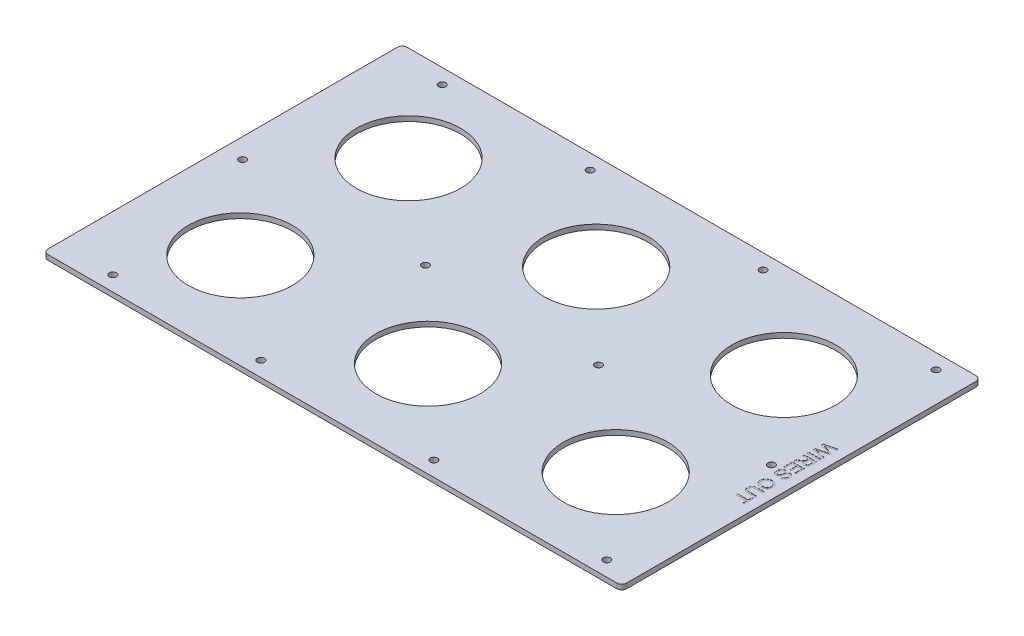
SolidWorks part; units mm, degrees
material "ABS"
ref_plane "Front" through (0, 0, 0) normal (0, 0, 1) x (1, 0, 0)
ref_plane "Top" through (0, 0, 0) normal (0, 1, 0) x (1, 0, 0)
ref_plane "Right" through (0, 0, 0) normal (1, 0, 0) x (0, 0, -1)
sketch "Sketch1" plane through (0, 0, 0) normal (0, 1, 0) x (1, 0, 0)
  line L1 (-180.975, 114.3) -> (180.975, 114.3)
  line L2 (-184.15, 111.125) -> (-184.15, -111.125)
  line L3 (-180.975, -114.3) -> (180.975, -114.3)
  line L4 (184.15, 111.125) -> (184.15, -111.125)
  line L5 (-184.15, 114.3) -> (184.15, -114.3) construction
  line L6 (-184.15, -114.3) -> (184.15, 114.3) construction
  circle A0 centre (119.5086, -53.5178) radius 33.147
  arc A1 (-184.15, -111.125) -> (-180.975, -114.3) centre (-180.975, -111.125) ccw
  arc A2 (180.975, -114.3) -> (184.15, -111.125) centre (180.975, -111.125) ccw
  arc A3 (184.15, 111.125) -> (180.975, 114.3) centre (180.975, 111.125) ccw
  arc A4 (-180.975, 114.3) -> (-184.15, 111.125) centre (-180.975, 111.125) ccw
  circle A5 centre (165.1, 0) radius 2.2479 construction
  circle A6 centre (165.1, 0) radius 2.2479
  circle A7 centre (-171.45, 0) radius 2.2479 construction
  circle A8 centre (-171.45, 0) radius 2.2479
  circle A21 centre (-55.0333, 0) radius 2.2479 construction
  circle A22 centre (55.0333, 0) radius 2.2479 construction
  circle A23 centre (-55.0333, 0) radius 2.2479
  circle A24 centre (55.0333, 0) radius 2.2479
  circle A25 centre (119.5086, 53.5178) radius 33.147
  circle A26 centre (0.0643, 53.5178) radius 33.147
  circle A27 centre (0.0643, -53.5178) radius 33.147
  circle A28 centre (-119.38, 53.5178) radius 33.147
  circle A29 centre (-119.38, -53.5178) radius 33.147
  arc A34 (-143.7521, 103.8733) -> (-143.7521, 3.1623) centre (-119.38, 53.5178) ccw construction
  arc A35 (-24.3078, 103.8733) -> (-24.3078, 3.1623) centre (0.0643, 53.5178) ccw construction
  arc A36 (95.1365, 103.8733) -> (95.1365, 3.1623) centre (119.5086, 53.5178) ccw construction
  arc A37 (-143.7521, -3.1623) -> (-143.7521, -103.8733) centre (-119.38, -53.5178) ccw construction
  arc A38 (-24.3078, -3.1623) -> (-24.3078, -103.8733) centre (0.0643, -53.5178) ccw construction
  arc A39 (95.1365, -3.1623) -> (95.1365, -103.8733) centre (119.5086, -53.5178) ccw construction
  circle A40 centre (-149.225, -104.775) radius 2.2479 construction
  circle A41 centre (-55.0333, -104.775) radius 2.2479 construction
  circle A42 centre (55.0333, -104.775) radius 2.2479 construction
  circle A43 centre (165.1, -104.775) radius 2.2479 construction
  circle A44 centre (-149.225, 104.775) radius 2.2479 construction
  circle A45 centre (-55.0333, 104.775) radius 2.2479 construction
  circle A46 centre (55.0333, 104.775) radius 2.2479 construction
  circle A47 centre (165.1, 104.775) radius 2.2479 construction
  circle A48 centre (-149.225, -104.775) radius 2.2479
  circle A49 centre (-55.0333, -104.775) radius 2.2479
  circle A50 centre (55.0333, -104.775) radius 2.2479
  circle A51 centre (165.1, -104.775) radius 2.2479
  circle A52 centre (-149.225, 104.775) radius 2.2479
  circle A53 centre (-55.0333, 104.775) radius 2.2479
  circle A54 centre (55.0333, 104.775) radius 2.2479
  circle A55 centre (165.1, 104.775) radius 2.2479
  point P0 (0, 0)
  dimension "D3" = 66.294
  dimension "D4" = 3.175
  dimension "D1" = 368.3
  dimension "D2" = 228.6
extrude "Boss-Extrude1" add sketch "Sketch1" along normal blind 3.175
sketch "Sketch2" plane through (0, 3.175, 0) normal (0, 1, 0) x (1, 0, 0)
  line L0 (170.15, 30) -> (170.15, -30) construction
  line L1 (0, 0) -> (184.15, 0) construction
  line L2 (184.15, -111.125) -> (184.15, 111.125) construction
  text T0 "WIRES OUT" font "Arial" height in points 30
  point P7 (170.15, 0)
  dimension "D1" = 14
  dimension "D2" = 60
extrude "Cut-Extrude1" cut sketch "Sketch2" against normal blind 0.1
